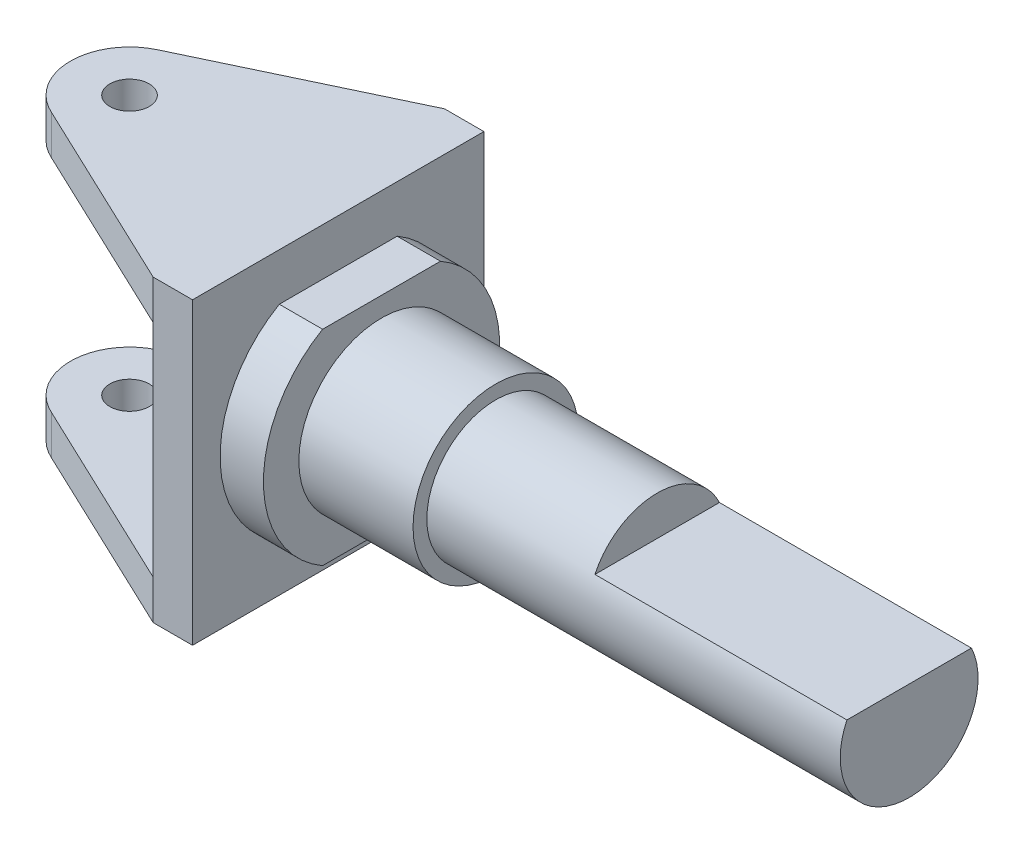
SolidWorks part; units mm, degrees
ref_plane "정면" through (0, 0, 0) normal (0, 0, 1) x (1, 0, 0)
ref_plane "윗면" through (0, 0, 0) normal (0, 1, 0) x (1, 0, 0)
ref_plane "우측면" through (0, 0, 0) normal (1, 0, 0) x (0, 0, -1)
sketch "스케치1" plane through (0, 0, 0) normal (0, 1, 0) x (1, 0, 0)
  line L0 (-70.1214, 0) -> (119.3908, 0) construction
  line L1 (-70.1214, 30) -> (-70.1214, -30)
  line L2 (-70.1214, -30) -> (-59.1214, -30)
  line L3 (-70.1214, 30) -> (-59.1214, 30)
  line L4 (-59.1214, -30) -> (-59.1214, -21)
  line L5 (-59.1214, 30) -> (-59.1214, 21)
  line L6 (-59.1214, -21) -> (-30.1214, -21)
  line L7 (-59.1214, 21) -> (-30.1214, 21)
  line L8 (-30.1214, -21) -> (-30.1214, -17.5)
  line L9 (-30.1214, 21) -> (-30.1214, 17.5)
  line L10 (-30.1214, -17.5) -> (74.8786, -17.5)
  line L11 (-30.1214, 17.5) -> (74.8786, 17.5)
  line L12 (74.8786, -17.5) -> (74.8786, 17.5)
  point P15 (74.8786, 0)
  dimension "D1" = 105
  dimension "D2" = 134
  dimension "D3" = 145
  dimension "D4" = 30
  dimension "D5" = 21
  dimension "D6" = 17.5
revolve "회전1" add sketch "스케치1" angle 360 about L0 region at (-2.6576, 0, 9.8767)
sketch "스케치2" plane through (74.8786, 0, 0) normal (1, 0, 0) x (0, 0, -1)
  line L0 (-15.8114, 7.5) -> (15.8114, 7.5)
  circle A0 centre (0, 0) radius 17.5 construction
  arc A1 (15.8114, 7.5) -> (-15.8114, 7.5) centre (0, 0) ccw
  circle M1 centre (0, 0) radius 17.5
  dimension "D1" = 7.5
extrude "컷-돌출1" cut sketch "스케치2" against normal blind 64 contours L0 M1 region at (74.8786, 11.6177, 0)
sketch "스케치3" plane through (-70.1214, 0, 0) normal (-1, 0, 0) x (0, 0, 1)
  line L0 (0, 0) -> (-36.5574, 0) construction
  line L1 (-14.9666, 26) -> (14.9666, 26)
  line L2 (-14.9666, -26) -> (14.9666, -26)
  circle A0 centre (0, 0) radius 30 construction
  arc A1 (-14.9666, -26) -> (14.9666, -26) centre (0, 0) ccw
  arc A2 (14.9666, 26) -> (-14.9666, 26) centre (0, 0) ccw
  circle M4 centre (0, 0) radius 30
  dimension "D1" = 52
extrude "컷-돌출2" cut sketch "스케치3" against normal blind 64 contours L2 M4 | L1 M4 region at (-70.1214, 27.6095, 0) region at (-70.1214, -27.6095, 0)
sketch "스케치4" plane through (-70.1214, 0, 0) normal (-1, 0, 0) x (0, 0, 1)
  line L1 (-37, -38) -> (37, -38)
  line L2 (-37, -38) -> (-37, 38)
  line L3 (-37, 38) -> (37, 38)
  line L4 (37, -38) -> (37, 38)
  line L5 (-37, -38) -> (37, 38) construction
  line L6 (-37, 38) -> (37, -38) construction
  point P1 (0, 0)
  arc M5 (-14.9666, 26) -> (-14.9666, -26) centre (0, 0) ccw
  line M6 (-14.9666, -26) -> (14.9666, -26)
  arc M7 (14.9666, -26) -> (14.9666, 26) centre (0, 0) ccw
  line M8 (14.9666, 26) -> (-14.9666, 26)
  dimension "D1" = 74
  dimension "D2" = 76
extrude "보스-돌출1" add sketch "스케치4" along normal blind 10 contours L1 L4 L3 L2 M5 M8 M7 M6 | M8 M5 M6 M7 region at (-70.1214, 0, -35.9392) region at (-70.1214, 0, 0)
sketch "스케치5" plane through (0, 38, 0) normal (0, 1, 0) x (1, 0, 0)
  line L0 (-80.1214, 37) -> (-129.5503, 13.5525)
  line L1 (-80.1214, -37) -> (-129.2495, -13.6911)
  line L2 (-80.1214, 37) -> (-80.1214, -37) construction
  arc A0 (-129.5503, 13.5525) -> (-129.2495, -13.6911) centre (-123.1214, 0) ccw
  circle A1 centre (-123.1214, 0) radius 5
  line M5 (-80.1214, 37) -> (-80.1214, -37)
  dimension "D1" = 37
  dimension "D3" = 30
  dimension "D4" = 10
  dimension "D2" = 43
extrude "보스-돌출2" add sketch "스케치5" against normal blind 10 from offset 66 contours L0 A0 L1 A1 M5 region at (-102.4088, 38, -0.0008) offset against normal yes
extrude "보스-돌출3" add sketch "스케치5<3>" against normal blind 10 contours L0 A0 L1 A1 M5 region at (-102.4088, 38, -0.0008)
sketch "스케치5<3>" plane through (0, 38, 0) normal (0, 1, 0) x (1, 0, 0) same geometry as "스케치5"
